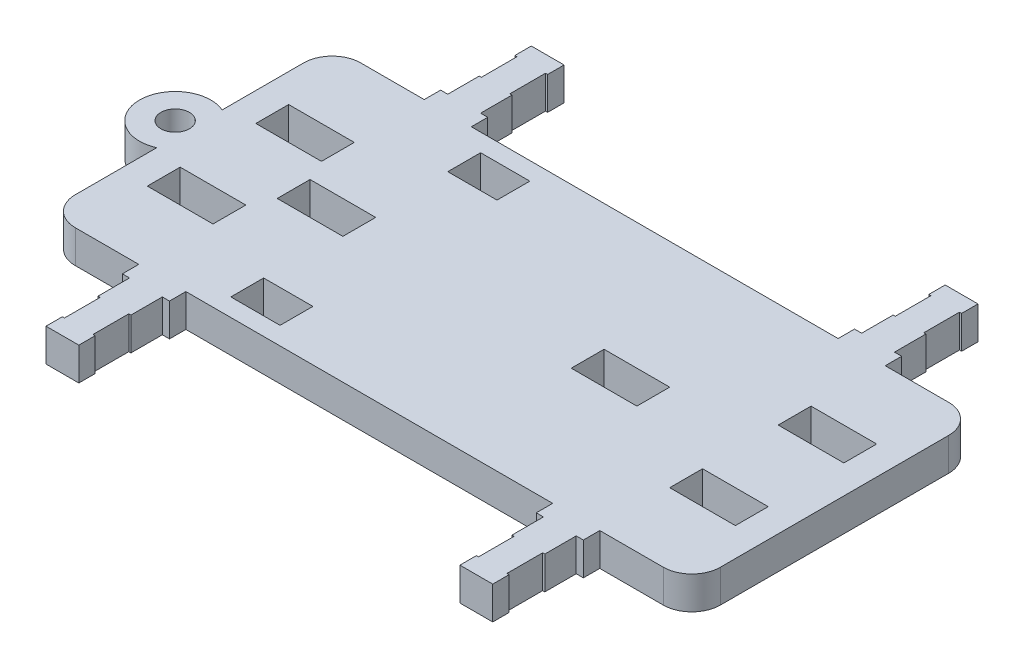
SolidWorks part; units mm, degrees
ref_plane "Front Plane" through (0, 0, 0) normal (0, 0, 1) x (1, 0, 0)
ref_plane "Top Plane" through (0, 0, 0) normal (0, 1, 0) x (1, 0, 0)
ref_plane "Right Plane" through (0, 0, 0) normal (1, 0, 0) x (0, 0, -1)
sketch "Sketch1" plane through (0, 0, 0) normal (0, 1, 0) x (1, 0, 0)
  line L1 (-20.6, -10) -> (20.6, -10)
  line L2 (-22.6, -8) -> (-22.6, 8)
  line L3 (-20.6, 10) -> (20.6, 10)
  line L4 (22.6, -8) -> (22.6, 8)
  line L5 (-22.6, -10) -> (22.6, 10) construction
  line L6 (-22.6, 10) -> (22.6, -10) construction
  arc A0 (20.6, 10) -> (22.6, 8) centre (20.6, 8) cw
  arc A1 (20.6, -10) -> (22.6, -8) centre (20.6, -8) ccw
  arc A2 (-20.6, -10) -> (-22.6, -8) centre (-20.6, -8) cw
  arc A3 (-22.6, 8) -> (-20.6, 10) centre (-20.6, 8) cw
  point P0 (0, 0)
  point P6 (0, 0)
  point P7 (0, 0)
  dimension "D15" = 2
  dimension "D1" = 20
  dimension "D2" = 45.2
base flange "Base-Flange1" sketch "Sketch1" thickness 2.3 reverse thickness direction no parameters "D1"=0.7366
sketch "Sketch12" plane through (0, 0, 0) normal (0, 1, 0) x (1, 0, 0)
  line L0 (0, 0) -> (13.3626, 0) construction
  line L1 (0, 0) -> (0, 10) construction
  line L2 (-15.3, -1.15) -> (-10.7, -1.15)
  line L3 (-15.3, -1.15) -> (-15.3, 1.15)
  line L4 (-15.3, 1.15) -> (-10.7, 1.15)
  line L5 (-10.7, -1.15) -> (-10.7, 1.15)
  line L6 (-15.3, -1.15) -> (-10.7, 1.15) construction
  line L7 (-15.3, 1.15) -> (-10.7, -1.15) construction
  line L8 (5.3, -1.15) -> (9.9, -1.15)
  line L9 (5.3, -1.15) -> (5.3, 1.15)
  line L10 (5.3, 1.15) -> (9.9, 1.15)
  line L11 (9.9, -1.15) -> (9.9, 1.15)
  line L12 (5.3, -1.15) -> (9.9, 1.15) construction
  line L13 (5.3, 1.15) -> (9.9, -1.15) construction
  line L16 (-16, 2.65) -> (-20.6, 2.65)
  line L17 (-16, 2.65) -> (-16, 4.95)
  line L18 (-16, 4.95) -> (-20.6, 4.95)
  line L19 (-20.6, 2.65) -> (-20.6, 4.95)
  line L20 (20.6, 2.65) -> (20.6, 4.95)
  line L21 (16, 4.95) -> (20.6, 4.95)
  line L22 (16, 2.65) -> (16, 4.95)
  line L23 (16, 2.65) -> (20.6, 2.65)
  line L24 (-20.6, -2.65) -> (-20.6, -4.95)
  line L25 (-16, -4.95) -> (-20.6, -4.95)
  line L26 (-16, -2.65) -> (-16, -4.95)
  line L27 (-16, -2.65) -> (-20.6, -2.65)
  line L28 (16, -2.65) -> (20.6, -2.65)
  line L29 (16, -2.65) -> (16, -4.95)
  line L30 (16, -4.95) -> (20.6, -4.95)
  line L31 (20.6, -2.65) -> (20.6, -4.95)
  line L33 (-10.95, 8.75) -> (-7.5, 8.75)
  line L34 (-10.95, 8.75) -> (-10.95, 6.45)
  line L35 (-10.95, 6.45) -> (-7.5, 6.45)
  line L36 (-7.5, 8.75) -> (-7.5, 6.45)
  line L37 (-10.95, -6.45) -> (-7.5, -6.45)
  line L38 (-7.5, -8.75) -> (-7.5, -6.45)
  line L39 (-10.95, -8.75) -> (-7.5, -8.75)
  line L40 (-10.95, -8.75) -> (-10.95, -6.45)
  point P1 (-13, 0)
  point P9 (7.6, 0)
  point P22 (0, 0)
  point P37 (0, 0)
  dimension "D1" = 2.3
  dimension "D2" = 4.6
  dimension "D3" = 16
  dimension "D4" = 0.7
  dimension "D5" = 1.5
  dimension "D6" = 16
  dimension "D7" = 3.45
  dimension "D8" = 2.3
  dimension "D9" = 1.5
  dimension "D10" = 0.25
extrude "Cut-Extrude2" cut sketch "Sketch12" against normal up to next normal cut yes
sketch "Sketch6" plane through (0, 0, 0) normal (0, 1, 0) x (1, 0, 0)
  line L0 (-14.5, 3.45) -> (-14.5, 11.8798) construction
  line L2 (14.5, 3.45) -> (14.5, -3.45) construction
  line L5 (20.6, 10) -> (-20.6, 10) construction
  line L6 (-12.85, 17) -> (-16.15, 17)
  line L7 (-12.85, 17) -> (-12.85, 10)
  line L8 (-12.85, 10) -> (-16.15, 10)
  line L9 (-16.15, 17) -> (-16.15, 10)
  line L10 (-12.85, 17) -> (-16.15, 10) construction
  line L11 (-12.85, 10) -> (-16.15, 17) construction
  line L12 (-20.6, -10) -> (20.6, -10) construction
  line L13 (16.15, 17) -> (12.85, 17)
  line L14 (16.15, 17) -> (16.15, 10)
  line L15 (16.15, 10) -> (12.85, 10)
  line L16 (12.85, 17) -> (12.85, 10)
  line L17 (16.15, 17) -> (12.85, 10) construction
  line L18 (16.15, 10) -> (12.85, 17) construction
  line L19 (16.15, -17) -> (12.85, -17)
  line L20 (16.15, -17) -> (16.15, -10)
  line L21 (16.15, -10) -> (12.85, -10)
  line L22 (12.85, -17) -> (12.85, -10)
  line L23 (16.15, -17) -> (12.85, -10) construction
  line L24 (16.15, -10) -> (12.85, -17) construction
  line L26 (-16.15, -17) -> (-12.85, -17)
  line L27 (-16.15, -17) -> (-16.15, -10)
  line L28 (-16.15, -10) -> (-12.85, -10)
  line L29 (-12.85, -17) -> (-12.85, -10)
  line L30 (-16.15, -17) -> (-12.85, -10) construction
  line L31 (-16.15, -10) -> (-12.85, -17) construction
  point P2 (-14.5, 13.5)
  point P11 (14.5, 13.5)
  point P16 (14.5, -13.5)
  point P23 (-14.5, -13.5)
  point P29 (0, 0)
  point P30 (0, 0)
  dimension "D1" = 3.3
  dimension "D2" = 7
  dimension "D3" = 14.5
  dimension "D4" = 14.5
base flange "Tab1" sketch "Sketch6" thickness 2.3 reverse thickness direction no parameters "D1"=0.7366
sketch "Sketch9" plane through (0, 0, 0) normal (0, 1, 0) x (1, 0, 0)
  line L0 (-12.85, 11.15) -> (-13.35, 11.15)
  line L1 (-12.85, 10) -> (-12.85, 17) construction
  line L2 (-13.35, 11.15) -> (-13.35, 13.35)
  line L3 (-13.35, 13.35) -> (-13.5, 13.35)
  line L4 (-13.5, 13.35) -> (-13.5, 15.85)
  line L5 (-13.5, 15.85) -> (-13.35, 15.85)
  line L6 (-13.35, 15.85) -> (-13.35, 17)
  line L7 (-12.85, 17) -> (-16.15, 17) construction
  line L8 (-14.5, -3.45) -> (-14.5, 3.45) construction
  line L11 (-13.35, 17) -> (-12.85, 17)
  line L12 (-12.85, 17) -> (-12.85, 11.15)
  line L14 (-16.15, 17) -> (-16.15, 11.15)
  line L16 (-15.65, 17) -> (-16.15, 17)
  line L17 (-15.65, 15.85) -> (-15.65, 17)
  line L18 (-15.5, 15.85) -> (-15.65, 15.85)
  line L19 (-15.5, 13.35) -> (-15.5, 15.85)
  line L20 (-15.65, 13.35) -> (-15.5, 13.35)
  line L21 (-15.65, 11.15) -> (-15.65, 13.35)
  line L22 (-16.15, 11.15) -> (-15.65, 11.15)
  line L23 (0, 0) -> (-20.4568, 0) construction
  line L24 (-16.15, -11.15) -> (-15.65, -11.15)
  line L25 (-15.65, -11.15) -> (-15.65, -13.35)
  line L26 (-15.65, -13.35) -> (-15.5, -13.35)
  line L27 (-15.5, -13.35) -> (-15.5, -15.85)
  line L28 (-15.5, -15.85) -> (-15.65, -15.85)
  line L29 (-15.65, -15.85) -> (-15.65, -17)
  line L30 (-15.65, -17) -> (-16.15, -17)
  line L31 (-16.15, -17) -> (-16.15, -11.15)
  line L32 (-12.85, -17) -> (-12.85, -11.15)
  line L33 (-13.35, -17) -> (-12.85, -17)
  line L34 (-13.35, -15.85) -> (-13.35, -17)
  line L35 (-13.5, -15.85) -> (-13.35, -15.85)
  line L36 (-13.5, -13.35) -> (-13.5, -15.85)
  line L37 (-13.35, -13.35) -> (-13.5, -13.35)
  line L38 (-13.35, -11.15) -> (-13.35, -13.35)
  line L39 (-12.85, -11.15) -> (-13.35, -11.15)
  line L40 (0, 0) -> (0, 4.5723) construction
  line L42 (12.85, -11.15) -> (13.35, -11.15)
  line L43 (13.35, -11.15) -> (13.35, -13.35)
  line L44 (13.35, -13.35) -> (13.5, -13.35)
  line L45 (13.5, -13.35) -> (13.5, -15.85)
  line L46 (13.5, -15.85) -> (13.35, -15.85)
  line L47 (13.35, -15.85) -> (13.35, -17)
  line L48 (13.35, -17) -> (12.85, -17)
  line L49 (12.85, -17) -> (12.85, -11.15)
  line L50 (16.15, -17) -> (16.15, -11.15)
  line L51 (15.65, -17) -> (16.15, -17)
  line L52 (15.65, -15.85) -> (15.65, -17)
  line L53 (15.5, -15.85) -> (15.65, -15.85)
  line L54 (15.5, -13.35) -> (15.5, -15.85)
  line L55 (15.65, -13.35) -> (15.5, -13.35)
  line L56 (15.65, -11.15) -> (15.65, -13.35)
  line L57 (16.15, -11.15) -> (15.65, -11.15)
  line L58 (12.85, 17) -> (12.85, 11.15)
  line L59 (13.35, 17) -> (12.85, 17)
  line L60 (13.35, 15.85) -> (13.35, 17)
  line L61 (13.5, 15.85) -> (13.35, 15.85)
  line L62 (13.5, 13.35) -> (13.5, 15.85)
  line L63 (13.35, 13.35) -> (13.5, 13.35)
  line L64 (13.35, 11.15) -> (13.35, 13.35)
  line L65 (12.85, 11.15) -> (13.35, 11.15)
  line L66 (16.15, 11.15) -> (15.65, 11.15)
  line L67 (15.65, 11.15) -> (15.65, 13.35)
  line L68 (15.65, 13.35) -> (15.5, 13.35)
  line L69 (15.5, 13.35) -> (15.5, 15.85)
  line L70 (15.5, 15.85) -> (15.65, 15.85)
  line L71 (15.65, 15.85) -> (15.65, 17)
  line L72 (15.65, 17) -> (16.15, 17)
  line L73 (16.15, 17) -> (16.15, 11.15)
  point P24 (0, 0)
  point P29 (-14.5, 17)
  dimension "D1" = 1.15
  dimension "D2" = 1.15
  dimension "D3" = 2.5
  dimension "D4" = 2.2
  dimension "D5" = 0.15
extrude "Cut-Extrude1" cut sketch "Sketch9" against normal up to next normal cut yes
sketch "Sketch10" plane through (0, 0, 0) normal (0, 1, 0) x (1, 0, 0)
  line L0 (-22.6, 8) -> (-22.6, -8) construction
  circle A0 centre (-23.6, 0) radius 1
  circle A1 centre (-23.6, 0) radius 2.5
  dimension "D1" = 2
  dimension "D2" = 5
base flange "Tab2" sketch "Sketch10" thickness 2.3 reverse thickness direction no parameters "D1"=0.7366
sketch "Bend-Lines1" [suppressed] plane through (0, 0, 0) normal (0, 1, 0) x (1, 0, 0)
sketch "Bounding-Box1" [suppressed] plane through (0, 0, 0) normal (0, 1, 0) x (1, 0, 0)
sheet metal parameters "Sheet-Metal1" thickness 2.3 parameters "D1"=0.7366
flat pattern "Flat-Pattern1" [suppressed]
sketch "Bend-Lines2" plane through (0, 0, 0) normal (0, 1, 0) x (1, 0, 0)
sketch3d "Bounding-Box2" [suppressed]
  line L0 (2, 2, 0) -> (-43.2, 2, 0) construction
  line L1 (2, -18, 0) -> (-43.2, -18, 0) construction
  line L2 (2, 2, 0) -> (2, -18, 0) construction
  line L3 (-43.2, 2, 0) -> (-43.2, -18, 0) construction
sheet metal parameters "Sheet-Metal2" thickness 2.3 parameters "D1"=0.7366
flat pattern "Flat-Pattern2"
sketch "Bend-Lines3" plane through (0, 0, 0) normal (0, 1, 0) x (1, 0, 0)
sketch3d "Bounding-Box3" [suppressed]
  line L0 (2, 9, 0) -> (-43.2, 9, 0) construction
  line L1 (2, -25, 0) -> (-43.2, -25, 0) construction
  line L2 (2, 9, 0) -> (2, -25, 0) construction
  line L3 (-43.2, 9, 0) -> (-43.2, -25, 0) construction
sheet metal parameters "Sheet-Metal3" thickness 2.3 parameters "D1"=0.7366
flat pattern "Flat-Pattern2"
sketch "Bend-Lines3" plane through (0, 0, 0) normal (0, 1, 0) x (1, 0, 0)
sketch3d "Bounding-Box3" [suppressed]
  line L0 (2, 9, 0) -> (-43.2, 9, 0) construction
  line L1 (2, -25, 0) -> (-43.2, -25, 0) construction
  line L2 (2, 9, 0) -> (2, -25, 0) construction
  line L3 (-43.2, 9, 0) -> (-43.2, -25, 0) construction
sheet metal parameters "Sheet-Metal4" thickness 2.3 parameters "D1"=0.7366
flat pattern "Flat-Pattern4"
sketch "Bend-Lines4" plane through (0, 0, 0) normal (0, 1, 0) x (1, 0, 0)
sketch3d "Bounding-Box4" [suppressed]
  line L0 (2, 9, 0) -> (-46.6996, 9, 0) construction
  line L1 (2, -25, 0) -> (-46.6996, -25, 0) construction
  line L2 (2, 9, 0) -> (2, -25, 0) construction
  line L3 (-46.6996, 9, 0) -> (-46.6996, -25, 0) construction
sheet metal parameters "Sheet-Metal5" thickness 2.3 parameters "D1"=0.7366
flat pattern "Flat-Pattern1"
sketch "Bend-Lines2" plane through (0, 0, 0) normal (0, 1, 0) x (1, 0, 0)
sketch3d "Bounding-Box2" [suppressed]
  line L0 (2, 2, 0) -> (-43.2, 2, 0) construction
  line L1 (2, -18, 0) -> (-43.2, -18, 0) construction
  line L2 (2, 2, 0) -> (2, -18, 0) construction
  line L3 (-43.2, 2, 0) -> (-43.2, -18, 0) construction
